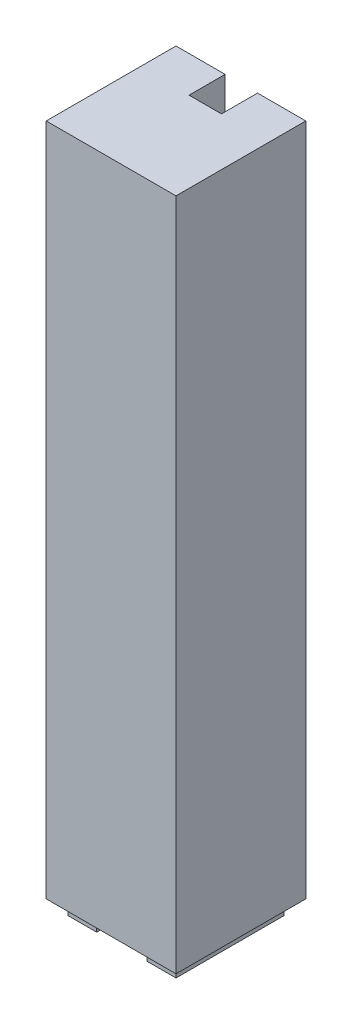
SolidWorks part; units mm, degrees
ref_plane "Front Plane" through (0, 0, 0) normal (0, 0, 1) x (1, 0, 0)
ref_plane "Top Plane" through (0, 0, 0) normal (0, 1, 0) x (1, 0, 0)
ref_plane "Right Plane" through (0, 0, 0) normal (1, 0, 0) x (0, 0, -1)
sketch "Sketch1" plane through (0, 0, 0) normal (0, 1, 0) x (1, 0, 0)
  line L1 (0, 0) -> (36, 0)
  line L2 (0, 0) -> (0, 36)
  line L3 (0, 36) -> (36, 36)
  line L4 (36, 0) -> (36, 36)
  dimension "D1" = 36
  dimension "D2" = 36
extrude "Boss-Extrude1" add sketch "Sketch1" along normal blind 186.9
sketch "Sketch2" plane through (0, 0, 0) normal (0, -1, 0) x (1, 0, 0)
  line L0 (0, 0) -> (36, 0) construction
  line L1 (3, -3) -> (7, -3)
  line L2 (3, -3) -> (3, -33)
  line L3 (3, -33) -> (7, -33)
  line L4 (7, -11) -> (7, -25)
  line L5 (36, -36) -> (0, -36) construction
  line L6 (0, -36) -> (0, 0) construction
  line L20 (36, 0) -> (36, -36) construction
  line L29 (7, -3) -> (11, -3)
  line L31 (7, -11) -> (11, -11)
  line L32 (11, -3) -> (11, -11)
  line L33 (7, -25) -> (11, -25)
  line L35 (7, -33) -> (11, -33)
  line L36 (11, -25) -> (11, -33)
  line L45 (29, -3) -> (33, -3)
  line L46 (29, -11) -> (29, -25)
  line L47 (29, -33) -> (33, -33)
  line L48 (33, -3) -> (33, -33)
  line L50 (29, -3) -> (25, -3)
  line L52 (29, -11) -> (25, -11)
  line L53 (25, -3) -> (25, -11)
  line L54 (29, -33) -> (25, -33)
  line L56 (29, -25) -> (25, -25)
  line L57 (25, -33) -> (25, -25)
  dimension "D1" = 3
  dimension "D2" = 3
  dimension "D3" = 3
  dimension "D4" = 4
  dimension "D5" = 4
  dimension "D6" = 8
  dimension "D7" = 8
  dimension "D8" = 4
  dimension "D9" = 3
  dimension "D10" = 3
  dimension "D11" = 3
  dimension "D12" = 4
  dimension "D13" = 4
  dimension "D14" = 4
extrude "Boss-Extrude2" add sketch "Sketch2" along normal blind 4
sketch "Sketch3" plane through (0, 0, 0) normal (0, -1, 0) x (1, 0, 0)
  line L0 (36, -36) -> (0, -36) construction
  line L2 (0, -36) -> (0, 0) construction
  circle A0 centre (18, -18) radius 2
  dimension "D1" = 4
  dimension "D2" = 18
  dimension "D3" = 18
extrude "Cut-Extrude1" cut sketch "Sketch3" against normal blind 5
sketch "Sketch4" plane through (0, 0, -36) normal (0, 0, 1) x (1, 0, 0)
  line L0 (0, 186.9) -> (36, 186.9) construction
  line L1 (13.62, 186.9) -> (22.62, 186.9)
  line L2 (13.62, 186.9) -> (13.62, 0)
  line L3 (13.62, 0) -> (22.62, 0)
  line L4 (22.62, 186.9) -> (22.62, 0)
  line L5 (0, 0) -> (36, 0) construction
  line L7 (36, 186.9) -> (36, 0) construction
  dimension "D1" = 13.38
  dimension "D2" = 9
extrude "Cut-Extrude2" cut sketch "Sketch4" along normal blind 10
